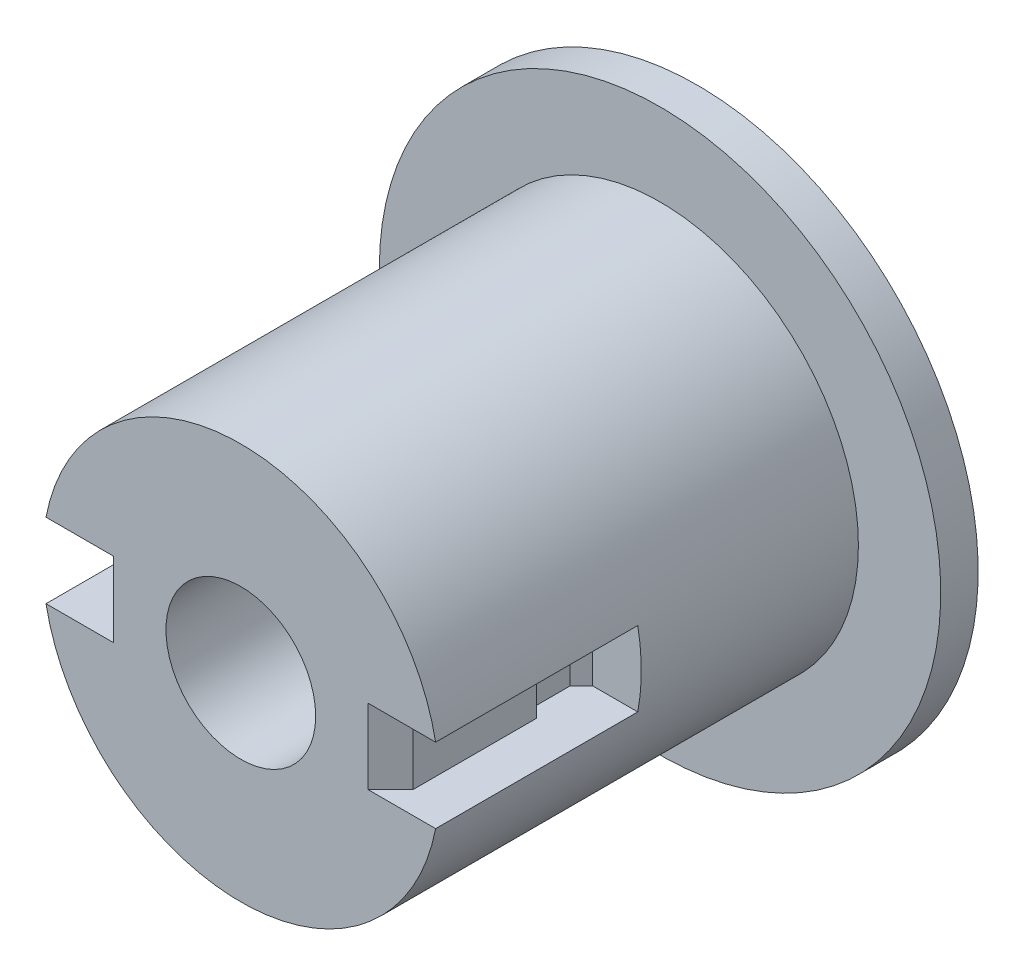
SolidWorks part; units mm, degrees
ref_plane "Front" through (0, 0, 0) normal (0, 0, 1) x (1, 0, 0)
ref_plane "Top" through (0, 0, 0) normal (0, 1, 0) x (1, 0, 0)
ref_plane "Right" through (0, 0, 0) normal (1, 0, 0) x (0, 0, -1)
sketch "Sketch1" plane through (0, 0, 0) normal (0, 0, 1) x (1, 0, 0)
  circle A0 centre (0, 0) radius 26.5
  dimension "D1" = 53
extrude "Boss-Extrude1" add sketch "Sketch1" along normal blind 56
sketch "Sketch4" plane through (0, 0, 0) normal (0, 0, -1) x (-1, 0, 0)
  circle A0 centre (0, 0) radius 37.5
  dimension "D1" = 75
extrude "Boss-Extrude2" add sketch "Sketch4" along normal blind 5
sketch "Sketch5" plane through (0, 0, 56) normal (0, 0, 1) x (1, 0, 0)
  circle A0 centre (0, 0) radius 10
  dimension "D1" = 20
extrude "Cut-Extrude1" cut sketch "Sketch5" against normal through all
sketch "Sketch6" plane through (0, 0, 0) normal (0, 1, 0) x (1, 0, 0)
  line L0 (20, -56) -> (26.5, -56)
  line L1 (26.5, -56) -> (26.5, -29)
  line L2 (26.5, -56) -> (26.5, 0) construction
  line L3 (26.5, -29) -> (20, -29)
  line L5 (18.5, -35) -> (20, -36.5)
  line L6 (20, -36.5) -> (20, -53)
  line L7 (20, -53) -> (17, -56)
  line L8 (17, -56) -> (20, -56)
  line L9 (20, -29) -> (18.5, -30.5)
  line L10 (18.5, -30.5) -> (18.5, -35)
  dimension "D1" = 3
  dimension "D2" = 6.5
  dimension "D3" = 8
  dimension "D4" = 27
  dimension "D5" = 7.5
  dimension "D6" = 3
  dimension "D7" = 135
  dimension "D8" = 135
extrude "Cut-Extrude2" cut sketch "Sketch6" against normal blind 5 and the other way blind 5 contours L9 L10 L5 L6 L7 L8 L0 L1 L3 region at (22.9613, 0, 42.3333)
mirror "Mirror1" about plane through (0, 0, 0) normal (1, 0, 0) of "Cut-Extrude2"
